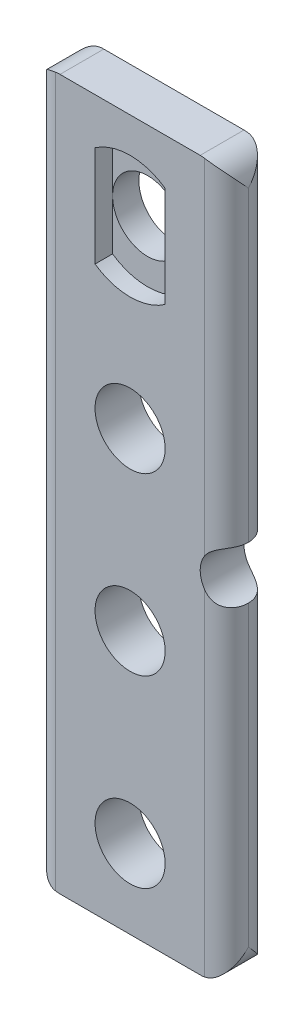
SolidWorks part; units mm, degrees
material "Acier galvanisé"
ref_plane "Plan de face" through (0, 0, 0) normal (0, 0, 1) x (1, 0, 0)
ref_plane "Plan de dessus" through (0, 0, 0) normal (0, 1, 0) x (1, 0, 0)
ref_plane "Plan de droite" through (0, 0, 0) normal (1, 0, 0) x (0, 0, -1)
sketch "Esquisse1" plane through (0, 0, 0) normal (0, 0, 1) x (1, 0, 0)
  line L0 (0, 0) -> (0, 83.2875) construction
  line L1 (-8, 0) -> (8, 0)
  line L2 (-11, 3) -> (-11, 78)
  line L3 (-8, 81) -> (8, 81)
  line L4 (11, 3) -> (11, 37)
  line L5 (11, 43) -> (11, 78)
  circle A0 centre (0, 9) radius 4
  circle A1 centre (0, 30) radius 4
  circle A2 centre (0, 50) radius 4
  circle A3 centre (0, 70) radius 4
  arc A4 (-11, 78) -> (-8, 81) centre (-8, 78) cw
  arc A5 (-8, 0) -> (-11, 3) centre (-8, 3) cw
  arc A6 (11, 3) -> (8, 0) centre (8, 3) cw
  arc A7 (8, 81) -> (11, 78) centre (8, 78) cw
  arc A8 (11, 43) -> (11, 37) centre (11, 40) ccw
  point P18 (-11, 0)
  point P21 (11, 0)
  point P24 (11, 81)
  dimension "D4" = 8
  dimension "D9" = 3
  dimension "D10" = 6
  dimension "D1" = 81
  dimension "D2" = 22
  dimension "D3" = 11
  dimension "D5" = 9
  dimension "D6" = 30
  dimension "D7" = 50
  dimension "D8" = 70
  dimension "D11" = 40
extrude "Extrusion1" add sketch "Esquisse1" along normal blind 5
sketch "Esquisse2" plane through (0, 0, 5) normal (0, 0, 1) x (1, 0, 0)
  line L0 (0, 78.426) -> (0, 60.7736) construction
  line L1 (4, 75.7446) -> (4, 64.2554)
  line L2 (-4, 75.7446) -> (-4, 64.2554)
  circle A0 centre (0, 70) radius 4 construction
  arc A1 (4, 75.7446) -> (-4, 75.7446) centre (0, 70) ccw
  arc A2 (-4, 64.2554) -> (4, 64.2554) centre (0, 70) ccw
  dimension "D1" = 14
extrude "Enlèv. mat.-Extru.1" cut sketch "Esquisse2" against normal blind 2
fillet "Congé1" radius 2.5 6 edges at (11, 20, 0) (-11, 40.5, 0) (11, 20, 5) (-11, 40.5, 5) (11, 60.5, 0) (11, 60.5, 5)
sketch "Esquisse3" [suppressed] plane through (0, 0, 0) normal (0, 0, 1) x (1, 0, 0)
  line L0 (0, 77.1623) -> (0, 63.2518)
  line L1 (6.2073, 82.8208) -> (-17.8413, 82.8208)
  line L2 (-17.8413, 48.1625) -> (-17.8413, 82.8208)
  line L3 (-21.1393, 43.8211) -> (19.481, 43.8211)
  line L4 (19.481, 43.8211) -> (19.481, -2.5849)
  line L5 (19.481, -2.5849) -> (-21.1393, -2.5849)
  line L6 (-21.1393, -2.5849) -> (-21.1393, 43.8211)
  spline_without_curve S0
  spline_without_curve S1
extrude "Enlèv. mat.-Extru.3" [suppressed] cut sketch "Esquisse3" along normal through all
